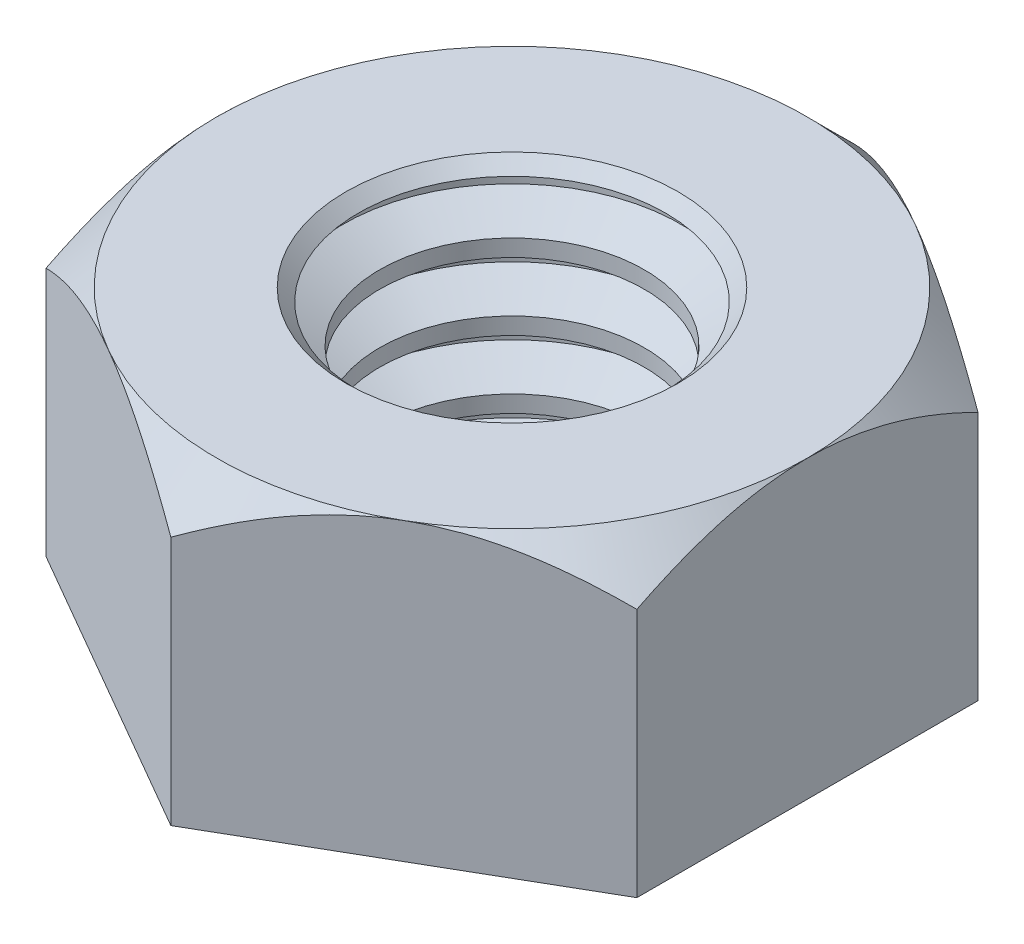
SolidWorks part; units mm, degrees
ref_plane "Front" through (0, 0, 0) normal (0, 0, 1) x (1, 0, 0)
ref_plane "Top" through (0, 0, 0) normal (0, 1, 0) x (1, 0, 0)
ref_plane "Right" through (0, 0, 0) normal (1, 0, 0) x (0, 0, -1)
sketch "Sketch1" plane through (0, 0, 0) normal (0, 1, 0) x (1, 0, 0)
  line L1 (0, 6.4158) -> (-5.5563, 3.2079)
  line L2 (-5.5563, 3.2079) -> (-5.5563, -3.2079)
  line L3 (-5.5563, -3.2079) -> (0, -6.4158)
  line L4 (0, -6.4158) -> (5.5562, -3.2079)
  line L5 (5.5562, -3.2079) -> (5.5562, 3.2079)
  line L6 (5.5562, 3.2079) -> (0, 6.4158)
  circle A0 centre (0, 0) radius 5.5563 construction
  dimension "Hex Flats" = 11.1125
extrude "Extrude1" add sketch "Sketch1" along normal blind 5.5562
sketch "Sketch3" plane through (0, 0, 0) normal (1, 0, 0) x (0, 0, -1)
  line L0 (5.5562, 5.5562) -> (6.4158, 4.6967)
  line L1 (3.2079, 5.5562) -> (6.4158, 5.5562) construction
  line L2 (6.4158, 5.5562) -> (6.4158, 0) construction
  line L3 (6.4158, 4.6967) -> (6.4158, 5.5562)
  line L4 (6.4158, 5.5562) -> (5.5562, 5.5562)
  line L5 (0, 0.542) -> (0, -0.542) construction
  dimension "D1" = 45
  dimension "D2" = 11.1125
revolve "Cut-Revolve2" cut sketch "Sketch3" angle 360 about L5
sketch "Sketch2" plane through (0, 0, 0) normal (0, 0, 1) x (1, 0, 0)
  line L0 (0, 1.6636) -> (0, -0.3796) construction
  line L1 (0, 5.5562) -> (2.4876, 5.5562)
  line L3 (0, 5.5562) -> (5.5562, 5.5562) construction
  line L4 (0, 4.2862) -> (2.4876, 4.2862)
  line L5 (2.4876, 5.5562) -> (3.175, 5.1594)
  line L6 (3.175, 5.1594) -> (3.175, 5.0006)
  line L7 (3.175, 5.0006) -> (2.4876, 4.6037)
  line L9 (2.4876, 4.2862) -> (2.4876, 4.6037)
  line L10 (0, 4.2862) -> (0, 5.5562)
  line L11 (2.4876, 5.5562) -> (2.4876, 4.6037) construction
  line L12 (3.175, 5.08) -> (2.4876, 5.08) construction
  dimension "D1" = 60
  dimension "D2" = 0.3175
  dimension "D5" = 0.1588
  dimension "Pitch" = 1.27
  dimension "Major Dia." = 6.35
revolve "Cut-Revolve1" cut sketch "Sketch2" angle 360 about L0
pattern_linear "LPattern2" count 5 spacing 1.27 along (0, -1, 0) of "Cut-Revolve1"
chamfer "Chamfer1" distance 0.635 angle 45 1 edges at (0, 5.5562, 2.4876) first distance on face at (0, 5.5563, 0)
equation "\"D5@Sketch2\"=\"Pitch@Sketch2\"/8"
equation "\"D2@Sketch2\"=\"Pitch@Sketch2\"/4"
equation "\"D3@LPattern2\"=\"Pitch@Sketch2\""
equation "\"D1@LPattern2\"=int(\"Height@Extrude1\"/\"Pitch@Sketch2\")+1"
equation "\"D2@Sketch3\"=\"Hex Flats@Sketch1\""
equation "\"D1@Chamfer1\"=\"Pitch@Sketch2\"/2"
